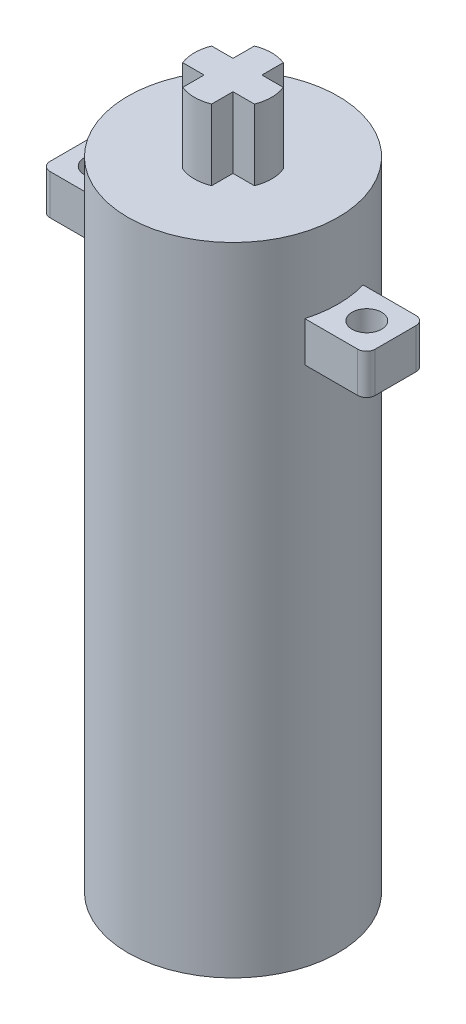
SolidWorks part; units mm, degrees
material "Plain Carbon Steel"
ref_plane "Front Plane" through (0, 0, 0) normal (0, 0, 1) x (1, 0, 0)
ref_plane "Top Plane" through (0, 0, 0) normal (0, 1, 0) x (1, 0, 0)
ref_plane "Right Plane" through (0, 0, 0) normal (1, 0, 0) x (0, 0, -1)
sketch "VigorSketch" plane through (0, 0, 0) normal (0, 1, 0) x (1, 0, 0)
  line L0 (0, -1.665) -> (0, 1.665)
  line L1 (-8.785, 1.665) -> (8.785, 1.665)
  line L2 (-9.285, 1.165) -> (-9.285, -1.165)
  line L3 (-8.785, -1.665) -> (8.785, -1.665)
  line L4 (9.285, 1.165) -> (9.285, -1.165)
  line L5 (2.0449, 0.8249) -> (0.8249, 0.8249)
  line L6 (0.8249, 0.8249) -> (0.8249, 2.0449)
  line L7 (-0.8249, 2.0449) -> (-0.8249, 0.8249)
  line L8 (-0.8249, 0.8249) -> (-2.0449, 0.8249)
  line L9 (-2.0449, -0.8249) -> (-0.8249, -0.8249)
  line L10 (-0.8249, -0.8249) -> (-0.8249, -2.0449)
  line L11 (2.0449, -0.8249) -> (0.8249, -0.8249)
  line L12 (0.8249, -0.8249) -> (0.8249, -2.0449)
  circle A0 centre (0, 0) radius 6
  arc A1 (-8.785, -1.665) -> (-9.285, -1.165) centre (-8.785, -1.165) cw
  arc A2 (9.285, -1.165) -> (8.785, -1.665) centre (8.785, -1.165) cw
  arc A3 (9.285, 1.165) -> (8.785, 1.665) centre (8.785, 1.165) ccw
  arc A4 (-8.785, 1.665) -> (-9.285, 1.165) centre (-8.785, 1.165) ccw
  circle A5 centre (7.6425, 0) radius 0.845
  circle A6 centre (-7.6425, 0) radius 0.845
  circle A7 centre (0, 0) radius 2.205
  point P7 (-9.285, 0)
  point P8 (9.285, 0)
  point P9 (0, 1.665)
  point P10 (0, -1.665)
  point P15 (9.285, -1.665)
  point P18 (9.285, 1.665)
  point P21 (-9.285, 1.665)
  point P40 (6, 0)
  dimension "D1" = 12
  dimension "D4" = 0.5
  dimension "D5" = 1.69
  dimension "D8" = 4.41
  dimension "D2" = 18.57
  dimension "D3" = 3.33
  dimension "D6" = 1.6425
  dimension "D7" = 1.665
  dimension "D9" = 1.22
extrude "VigorFlange" add sketch "VigorSketch" along normal blind 2.29 contours L1 A4 L2 A1 L3 A0 A6 | L1 A0 L3 L0 | L3 A0 L1 L0 | L4 A3 L1 A0 L3 A2 A5 region at (-3.9418, 0, 0) region at (3.9418, 0, 0) region at (-7.2747, 0, 1.6165) region at (5.9888, 0, 0.8476)
extrude "VigorAxle" add sketch "Sketch1<7>" along normal blind 10.62 contours L11 A7 L5 L6 L1 L0 L3 L12 | L8 A7 L9 L10 L3 L0 L1 L7 | L6 A7 L7 L1 | L10 A7 L12 L3 region at (-0.8902, 0, 0) region at (0, 0, 1.911) region at (0.8902, 0, 0) region at (0, 0, -1.911)
sketch "Sketch1<7>" plane through (0, 0, 0) normal (0, 1, 0) x (1, 0, 0) same geometry as "VigorSketch"
extrude "VigorBody" add sketch "VigorSketch<8>" along normal blind 6.58 and the other way blind 29.7899 contours A7 L1 A0 | A7 L3 A0 | L9 A7 L3 L10 | L1 A7 L8 L7 | L5 A7 L1 L6 | L3 A7 L11 L12 | L12 A7 L3 | L1 A7 L6 | L7 A7 L1 | L3 A7 L10 | A7 L1 A0 L3 | A7 L3 A0 L1 | L8 A7 L9 L10 L3 L0 L1 L7 | L11 A7 L5 L6 L1 L0 L3 L12 | L6 A7 L7 L1 | L10 A7 L12 L3 region at (-0.8902, 0, 0) region at (0, 0, 1.911) region at (0.8902, 0, 0) region at (0, 0, -1.911) region at (-1.044, 0, 1.7998) region at (-1.3254, 0, 1.2025) region at (1.3254, 0, 1.2025) region at (1.044, 0, 1.7998) region at (-1.3254, 0, -1.2025) region at (-1.044, 0, -1.7998) region at (1.044, 0, -1.7998) region at (1.3254, 0, -1.2025) region at (0, 0, 3.5146) region at (-3.9418, 0, 0) region at (3.9418, 0, 0) region at (0, 0, -3.5146)
sketch "VigorSketch<8>" plane through (0, 0, 0) normal (0, 1, 0) x (1, 0, 0) same geometry as "VigorSketch"
equation "\"vigorwidth\"= 0.472441in"
equation "\"D1@VigorSketch\"=\"vigorwidth\""
equation "\"vigorflangewidth\"= 0.731102in"
equation "\"D2@VigorSketch\"=\"vigorflangewidth\""
equation "\"vigorflangelength\"= 0.131102in"
equation "\"D3@VigorSketch\"=\"vigorflangelength\""
equation "\"vigorscrewsize\"= 0.066535in"
equation "\"D5@VigorSketch\"=\"vigorscrewsize\""
equation "\"vigorholeoffsetwid\"= 0.0646653in"
equation "\"D6@VigorSketch\"=\"vigorholeoffsetwid\""
equation "\"vigorholeoffsetlen\"= 0.065551in"
equation "\"D7@VigorSketch\"= \"vigorholeoffsetlen\""
equation "\"vigorflangedepth\"= 0.0901575in"
equation "\"vigordiscdepth\"= 0.0492126in"
equation "\"vigormotordepth\"= 1.12362in"
equation "\"vigortipdepth\"= 0.259055in"
equation "\"vigoraxlewidth\"= 0.173622in"
equation "\"D8@VigorSketch\"=\"vigoraxlewidth\""
equation "\"vigorcutlen\"= 0.0480315in"
equation "\"D9@VigorSketch\"=\"vigorcutlen\""
equation "\"vigoraxledepth\"= 0.159055in"
equation "\"D1@VigorBody\"=\"vigortipdepth\""
equation "\"D2@VigorBody\"=\"vigordiscdepth\"+\"vigormotordepth\""
equation "\"D1@VigorFlange\"=\"vigorflangedepth\""
equation "\"D1@VigorAxle\"=\"vigortipdepth\"+\"vigoraxledepth\""
